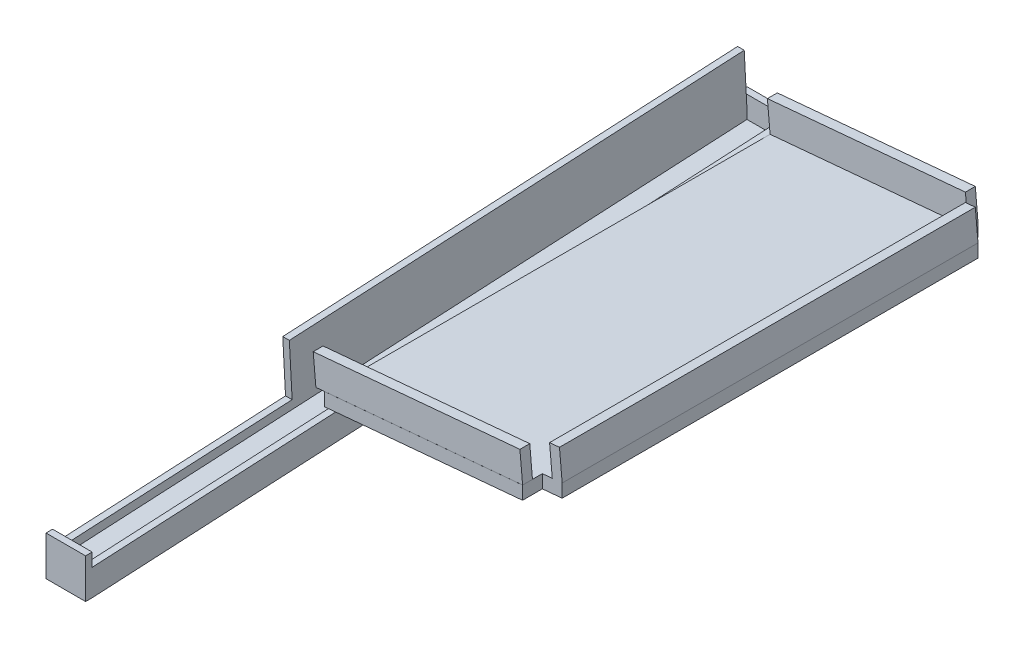
SolidWorks part; units mm, degrees
ref_plane "Front Plane" through (0, 0, 0) normal (0, 0, 1) x (1, 0, 0)
ref_plane "Top Plane" through (0, 0, 0) normal (0, 1, 0) x (1, 0, 0)
ref_plane "Right Plane" through (0, 0, 0) normal (1, 0, 0) x (0, 0, -1)
sketch "Sketch1" plane through (0, 0, 0) normal (0, 0, 1) x (1, 0, 0)
  line L0 (0, 0) -> (0, 20)
  line L1 (0, 0) -> (330, 0)
  line L2 (330, 0) -> (330, 50)
  line L3 (330, 50) -> (0, 20)
  line L4 (0, 0) -> (330, 30)
  dimension "D1" = 20
  dimension "D2" = 20
  dimension "D3" = 330
  dimension "D4" = 50
extrude "Boss-Extrude1" add sketch "Sketch1" along normal blind 690 contours L0 L4 L2 L3 region at (165, 25, 0)
sketch "Sketch3" plane through (0, 0, 0) normal (0, 1, 0) x (1, 0, 0)
  line L0 (300, -690) -> (330, -690)
  line L1 (330, -690) -> (330, -660)
  line L2 (330, -30) -> (330, 0)
  line L3 (330, -690) -> (300, -690)
  line L4 (330, -690) -> (330, -660)
  line L5 (330, -660) -> (300, -660)
  line L6 (300, -690) -> (300, -660)
  line L7 (330, 0) -> (300, 0)
  line L8 (330, 0) -> (330, -30)
  line L9 (330, -30) -> (300, -30)
  line L10 (300, 0) -> (300, -30)
  dimension "D2" = 30
  dimension "D3" = 30
  dimension "D4" = 30
  dimension "D5" = 30
  dimension "D6" = 690
extrude "Cut-Extrude2" cut sketch "Sketch3" along normal through all contours L6 L0 L1 L5 | L7 L10 L9 L2 region at (315, 0, 675) region at (315, 0, 15)
sketch "Sketch4" plane through (0, 0, 0) normal (-1, 0, 0) x (0, 0, 1)
  line L0 (0, 20) -> (0, 0)
  line L1 (1042, -34.6089) -> (1042, -54.6089)
  line L3 (0, 20) -> (1042, -34.6089)
  line L4 (1042, -54.6089) -> (1042, -74.6089)
  line L5 (1042, -74.6089) -> (0, -20)
  line L6 (0, -20) -> (0, 0)
  dimension "D1" = 40
  dimension "D2" = 20
  dimension "D3" = 40
  dimension "D4" = 87
  dimension "D5" = 1042
extrude "Boss-Extrude2" add sketch "Sketch4" along normal blind 60
sketch "Sketch6" plane through (0, 19.9452, 1.0453) normal (0, 0.9986, 0.0523) x (1, 0, 0)
  line L1 (-60, 1.0467) -> (0, 1.0467) construction
  line L2 (-50, 1.0467) -> (-50, -1042.3833)
  line L3 (-60, -1042.3833) -> (0, -1042.3833) construction
  line L4 (-50, -1042.3833) -> (-10, -1042.3833)
  line L5 (-10, -1042.3833) -> (-10, 1.0467)
  line L6 (-10, 1.0467) -> (-50, 1.0467)
  dimension "D1" = 10
  dimension "D2" = 10
extrude "Cut-Extrude3" cut sketch "Sketch6" against normal blind 13
sketch "Sketch7" plane through (0, -54.5541, 1040.9547) normal (0, 0.0523, -0.9986) x (-1, 0, 0)
  line L0 (10, 6.9726) -> (10, 19.9726)
  line L1 (10, 19.9726) -> (50, 19.9726)
  line L2 (50, 19.9726) -> (50, 6.9726)
  line L3 (50, 6.9726) -> (10, 6.9726)
extrude "Cut-Extrude4" cut sketch "Sketch7" against normal through all
sketch "Sketch8" plane through (0, 19.9452, 1.0453) normal (0, 0.9986, 0.0523) x (1, 0, 0)
  line L1 (-60, 1.0467) -> (-50, 1.0467)
  line L2 (-60, 1.0467) -> (-60, -689.0232)
  line L3 (-60, -689.0232) -> (-50, -689.0232)
  line L4 (-50, 1.0467) -> (-50, -689.0232)
  dimension "D1" = 690.0699
sketch "Sketch10" plane through (0, 0, 1042) normal (0, 0, 1) x (1, 0, 0)
  line L10 (-60, -14.6089) -> (0, -14.6089)
  line L11 (-60, -14.6089) -> (-60, -74.6089)
  line L12 (-60, -74.6089) -> (0, -74.6089)
  line L13 (0, -14.6089) -> (0, -74.6089)
  dimension "D1" = 60
extrude "Boss-Extrude4" add sketch "Sketch10" along normal blind 10
ref_plane "Plane1" through (0, -80, 0) normal (0, 1, 0) x (1, 0, 0)
sketch "Sketch16" plane through (-60, 0, 0) normal (-1, 0, 0) x (0, 0, 1)
  line L0 (0, -20) -> (0, -80)
  line L1 (214.5, -80) -> (-214.5, -80) construction
  line L2 (0, -80) -> (30, -80)
  line L3 (30, -80) -> (30, -21.5722)
  line L4 (0, -20) -> (1042, -74.6089) construction
  line L5 (521, -47.3045) -> (521, -80)
  line L6 (521, -80) -> (551, -80)
  line L7 (551, -80) -> (551, -48.8767)
  line L8 (521, -47.3045) -> (551, -48.8767)
  line L9 (0, -20) -> (30, -21.5722)
  dimension "D1" = 30
  dimension "D2" = 30
extrude "Boss-Extrude8" add sketch "Sketch16" against normal blind 30
sketch "Sketch17" plane through (-1.8033, 19.8361, 0) normal (-0.0905, 0.9959, 0) x (0.9959, 0.0905, 0)
  line L0 (1.8107, -690) -> (1.8107, 0) construction
  line L1 (1.8107, -15) -> (303.0478, -15)
  line L2 (1.8107, -15) -> (1.8107, 0)
  line L3 (1.8107, 0) -> (303.0478, 0)
  line L4 (303.0478, -15) -> (303.0478, 0)
  line L5 (333.1715, -660) -> (303.0478, -660) construction
  line L6 (333.1715, -30) -> (318.1097, -30)
  line L7 (333.1715, -30) -> (333.1715, -660)
  line L8 (333.1715, -660) -> (318.1097, -660)
  line L9 (318.1097, -30) -> (318.1097, -660)
  line L10 (303.0478, -690) -> (303.0478, -660) construction
  line L11 (303.0478, -675) -> (-11.4218, -675)
  line L12 (303.0478, -675) -> (303.0478, -689.9372)
  line L13 (303.0478, -689.9372) -> (-11.4218, -689.9372)
  line L14 (-11.4218, -675) -> (-11.4218, -689.9372)
  line L15 (303.0478, 0) -> (303.0478, -30) construction
  line L16 (-13.0923, -1042) -> (-8.1482, 0) construction
  line L17 (333.1715, -30) -> (303.0478, -30) construction
  point P11 (0, 0)
  point P21 (0, 0)
  point P35 (318.1097, -30)
  dimension "D1" = 314.4696
extrude "Boss-Extrude9" add sketch "Sketch17" along normal blind 45
extrude "Boss-Extrude10" add sketch "Sketch8" along normal blind 80 contours L4 L3 L2 L1
sketch "Sketch21" plane through (0, 0, 0) normal (0, 0, -1) x (-1, 0, 0)
  line L0 (60, 99.8904) -> (60, 20) construction
  line L1 (0, -20) -> (60, -20)
  line L2 (0, -20) -> (0, 40)
  line L3 (0, 40) -> (60, 40)
  line L4 (60, -20) -> (60, 40)
  dimension "D1" = 60
extrude "Boss-Extrude14" add sketch "Sketch21" along normal blind 10 separate body
